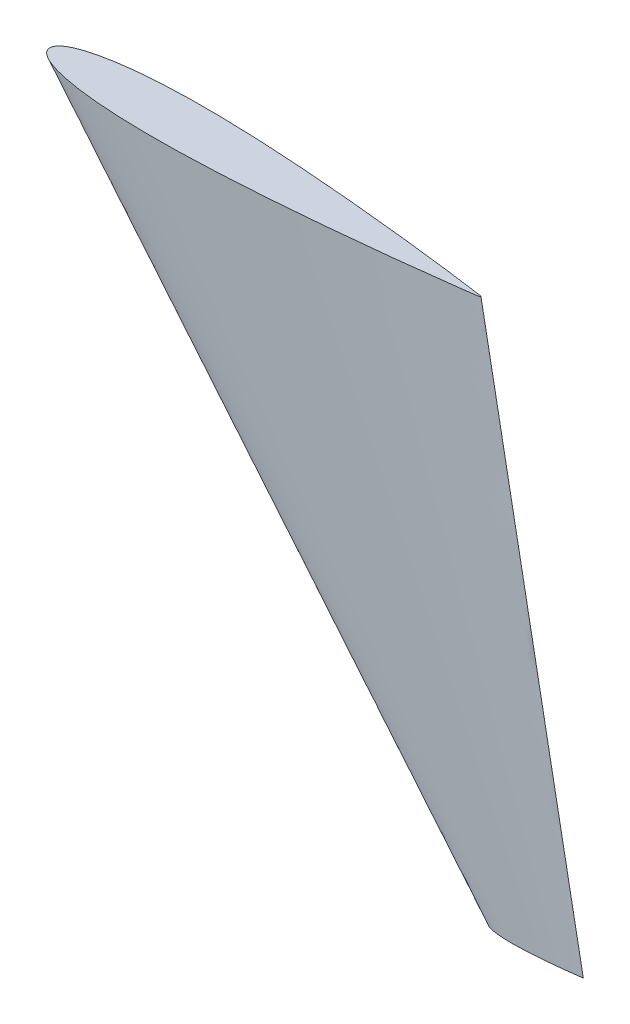
SolidWorks part; units mm, degrees
ref_plane "Front Plane" through (0, 0, 0) normal (0, 0, 1) x (1, 0, 0)
ref_plane "Top Plane" through (0, 0, 0) normal (0, 1, 0) x (1, 0, 0)
ref_plane "Right Plane" through (0, 0, 0) normal (1, 0, 0) x (0, 0, -1)
curve "Curve1"
  spline degree 3 poles (989.1889, 0, -3.124) (1003.9656, 0, 0) (989.1889, 0, 3.124) (979.4957, 0, 3.9602) (962.3964, 0, 6.4841) (943.9428, 0, 8.8491) (922.9132, 0, 11.6051) (900.2887, 0, 14.4478) (876.1894, 0, 17.4113) (850.9063, 0, 20.4351) (824.6249, 0, 23.4743) (797.5193, 0, 26.5234) (769.735, 0, 29.5334) (741.4059, 0, 32.5134) (712.6526, 0, 35.4198) (683.5857, 0, 38.2366) (654.3085, 0, 40.9505) (624.9168, 0, 43.5692) (595.4919, 0, 46.0176) (566.1196, 0, 48.3457) (536.8752, 0, 50.4873) (507.8364, 0, 52.4785) (479.0688, 0, 54.2437) (450.6418, 0, 55.8057) (422.6181, 0, 57.149) (395.0577, 0, 58.2561) (368.0197, 0, 59.0905) (341.5624, 0, 59.6944) (315.7376, 0, 59.999) (290.5993, 0, 60.0553) (266.1976, 0, 59.7899) (242.5818, 0, 59.2641) (219.7995, 0, 58.4267) (197.8965, 0, 57.3046) (176.9228, 0, 55.8955) (156.9193, 0, 54.1908) (137.9264, 0, 52.2182) (119.9888, 0, 49.9445) (103.1457, 0, 47.4173) (87.4377, 0, 44.6503) (72.9094, 0, 41.6113) (59.5881, 0, 38.3545) (47.5124, 0, 34.8789) (36.7185, 0, 31.1996) (27.2445, 0, 27.3184) (19.1092, 0, 23.264) (12.343, 0, 19.027) (6.9689, 0, 14.6049) (3.0199, 0, 9.972) (0.5665, 0, 5.0849) (-0.2745, 0, 0) (0.5665, 0, -5.0849) (3.0199, 0, -9.972) (6.9689, 0, -14.6049) (12.343, 0, -19.027) (19.1092, 0, -23.264) (27.2445, 0, -27.3184) (36.7185, 0, -31.1996) (47.5124, 0, -34.8789) (59.5881, 0, -38.3545) (72.9094, 0, -41.6113) (87.4377, 0, -44.6503) (103.1457, 0, -47.4173) (119.9888, 0, -49.9445) (137.9264, 0, -52.2182) (156.9193, 0, -54.1908) (176.9228, 0, -55.8955) (197.8965, 0, -57.3046) (219.7995, 0, -58.4267) (242.5818, 0, -59.2641) (266.1976, 0, -59.7899) (290.5993, 0, -60.0553) (315.7376, 0, -59.999) (341.5624, 0, -59.6944) (368.0197, 0, -59.0905) (395.0577, 0, -58.2561) (422.6181, 0, -57.149) (450.6418, 0, -55.8057) (479.0688, 0, -54.2437) (507.8364, 0, -52.4785) (536.8752, 0, -50.4873) (566.1196, 0, -48.3457) (595.4919, 0, -46.0176) (624.9168, 0, -43.5692) (654.3085, 0, -40.9505) (683.5857, 0, -38.2366) (712.6526, 0, -35.4198) (741.4059, 0, -32.5134) (769.735, 0, -29.5334) (797.5193, 0, -26.5234) (824.6249, 0, -23.4743) (850.9063, 0, -20.4351) (876.1894, 0, -17.4113) (900.2887, 0, -14.4478) (922.9132, 0, -11.6051) (943.9428, 0, -8.8491) (962.3964, 0, -6.4841) (979.4957, 0, -3.9602) (989.1889, 0, -3.124) (1003.9656, 0, 0) (989.1889, 0, 3.124) knots -0.01819 -0.010091 -0.003701 0 0.003701 0.010091 0.01819 0.027571 0.037978 0.04922 0.061159 0.073676 0.086676 0.10007 0.113795 0.12778 0.141967 0.156301 0.170733 0.185213 0.199702 0.214161 0.22855 0.24283 0.256971 0.270941 0.284704 0.298236 0.311509 0.32449 0.337159 0.349495 0.361463 0.373051 0.384237 0.394993 0.405307 0.415153 0.424519 0.43339 0.441745 0.449568 0.456846 0.463572 0.469733 0.475323 0.480337 0.484781 0.488676 0.492055 0.49498 0.497567 0.5 0.502433 0.50502 0.507945 0.511324 0.515219 0.519663 0.524677 0.530267 0.536428 0.543154 0.550432 0.558255 0.56661 0.575481 0.584847 0.594693 0.605007 0.615763 0.626949 0.638537 0.650505 0.662841 0.67551 0.688491 0.701764 0.715296 0.729059 0.743029 0.75717 0.77145 0.785839 0.800298 0.814787 0.829267 0.843699 0.858033 0.87222 0.886205 0.89993 0.913324 0.926324 0.938841 0.95078 0.962022 0.972429 0.98181 0.989909 0.996299 1 1.003701 1.010091 1.01819 periodic
sketch "Sketch2" plane through (0, 0, 0) normal (0, 1, 0) x (1, 0, 0)
  line L0 (8000, 0) -> (0, 0) construction
  line L1 (0, 0) -> (0, 395.0757) construction
  spline S1 degree 3 poles (7913.5111, -24.9917) (8031.7244, 0) (7913.5111, 24.9917) (7835.9656, 31.6818) (7699.1714, 51.8731) (7551.5421, 70.7926) (7383.3058, 92.8411) (7202.3097, 115.5825) (7009.5155, 139.2903) (6807.2507, 163.4811) (6596.999, 187.7941) (6380.1543, 212.1874) (6157.8798, 236.2671) (5931.2469, 260.1076) (5701.2206, 283.358) (5468.6854, 305.8929) (5234.4683, 327.6039) (4999.3345, 348.5532) (4763.9351, 368.1406) (4528.9569, 386.7656) (4295.002, 403.8987) (4062.6912, 419.8279) (3832.5502, 433.9494) (3605.1341, 446.4459) (3380.9452, 457.1923) (3160.4615, 466.0486) (2944.1578, 472.7239) (2732.499, 477.5553) (2525.9006, 479.9923) (2324.7946, 480.442) (2129.581, 478.3189) (1940.6547, 474.1131) (1758.3957, 467.4132) (1583.1723, 458.4372) (1415.3822, 447.1637) (1255.3541, 433.5267) (1103.4111, 417.7455) (959.9104, 399.5558) (825.1655, 379.3384) (699.5013, 357.2026) (583.2749, 332.8904) (476.7045, 306.8362) (380.0992, 279.0311) (293.7477, 249.5968) (217.9557, 218.5468) (152.8739, 186.1121) (98.7444, 152.2163) (55.7515, 116.8395) (24.1594, 79.7757) (4.532, 40.6789) (-2.1961, 0) (4.532, -40.6789) (24.1594, -79.7757) (55.7515, -116.8395) (98.7444, -152.2163) (152.8739, -186.1121) (217.9557, -218.5468) (293.7477, -249.5968) (380.0992, -279.0311) (476.7045, -306.8362) (583.2749, -332.8904) (699.5013, -357.2026) (825.1655, -379.3384) (959.9104, -399.5558) (1103.4111, -417.7455) (1255.3541, -433.5267) (1415.3822, -447.1637) (1583.1723, -458.4372) (1758.3957, -467.4132) (1940.6547, -474.1131) (2129.581, -478.3189) (2324.7946, -480.442) (2525.9006, -479.9923) (2732.499, -477.5553) (2944.1578, -472.7239) (3160.4615, -466.0486) (3380.9452, -457.1923) (3605.1341, -446.4459) (3832.5502, -433.9494) (4062.6912, -419.8279) (4295.002, -403.8987) (4528.9569, -386.7656) (4763.9351, -368.1406) (4999.3345, -348.5532) (5234.4683, -327.6039) (5468.6854, -305.8929) (5701.2206, -283.358) (5931.2469, -260.1076) (6157.8798, -236.2671) (6380.1543, -212.1874) (6596.999, -187.7941) (6807.2507, -163.4811) (7009.5155, -139.2903) (7202.3097, -115.5825) (7383.3058, -92.8411) (7551.5421, -70.7926) (7699.1714, -51.8731) (7835.9656, -31.6818) (7913.5111, -24.9917) (8031.7244, 0) (7913.5111, 24.9917) knots -0.01819 -0.010091 -0.003701 0 0.003701 0.010091 0.01819 0.027571 0.037978 0.04922 0.061159 0.073676 0.086676 0.10007 0.113795 0.12778 0.141967 0.156301 0.170733 0.185213 0.199702 0.214161 0.22855 0.24283 0.256971 0.270941 0.284704 0.298236 0.311509 0.32449 0.337159 0.349495 0.361463 0.373051 0.384237 0.394993 0.405307 0.415153 0.424519 0.43339 0.441745 0.449568 0.456846 0.463572 0.469733 0.475323 0.480337 0.484781 0.488676 0.492055 0.49498 0.497567 0.5 0.502433 0.50502 0.507945 0.511324 0.515219 0.519663 0.524677 0.530267 0.536428 0.543154 0.550432 0.558255 0.56661 0.575481 0.584847 0.594693 0.605007 0.615763 0.626949 0.638537 0.650505 0.662841 0.67551 0.688491 0.701764 0.715296 0.729059 0.743029 0.75717 0.77145 0.785839 0.800298 0.814787 0.829267 0.843699 0.858033 0.87222 0.886205 0.89993 0.913324 0.926324 0.938841 0.95078 0.962022 0.972429 0.98181 0.989909 0.996299 1 1.003701 1.010091 1.01819 only from (8000, 0) to (8000, 0)
  point P1 (0, 0)
  point P4 (0, 0)
  dimension "D1" = 8000
ref_plane "Plane1" through (0, -10000, 0) normal (0, 1, 0) x (1, 0, 0)
sketch "Sketch6" plane through (0, -10000, 0) normal (0, 1, 0) x (1, 0, 0)
  line L0 (9900, 0) -> (8150, 0) construction
  line L1 (8150, 0) -> (8150, 213.2137) construction
  line L2 (8000, 0) -> (0, 0) construction
  spline S1 degree 3 poles (9881.0805, -5.4669) (9906.9397, 0) (9881.0805, 5.4669) (9864.1175, 6.9304) (9834.1938, 11.3472) (9801.8998, 15.4859) (9765.0981, 20.309) (9725.5052, 25.2837) (9683.3315, 30.4697) (9639.0861, 35.7615) (9593.0935, 41.08) (9545.6587, 46.416) (9497.0362, 51.6834) (9447.4603, 56.8985) (9397.142, 61.9846) (9346.2749, 66.9141) (9295.0399, 71.6633) (9243.6044, 76.246) (9192.1108, 80.5308) (9140.7093, 84.605) (9089.5317, 88.3528) (9038.7137, 91.8374) (8988.3704, 94.9264) (8938.6231, 97.66) (8889.5818, 100.0108) (8841.3509, 101.9481) (8794.0345, 103.4083) (8747.7342, 104.4652) (8702.5408, 104.9983) (8658.5488, 105.0967) (8615.8458, 104.6323) (8574.5182, 103.7122) (8534.6491, 102.2466) (8496.3189, 100.2831) (8459.6149, 97.8171) (8424.6087, 94.834) (8391.3712, 91.3818) (8359.9804, 87.4028) (8330.505, 82.9803) (8303.0159, 78.1381) (8277.5914, 72.8198) (8254.2791, 67.1204) (8233.1467, 61.038) (8214.2573, 54.5993) (8197.6778, 47.8071) (8183.4412, 40.712) (8171.6003, 33.2973) (8162.1956, 25.5586) (8155.2849, 17.4509) (8150.9914, 8.8985) (8149.5196, 0) (8150.9914, -8.8985) (8155.2849, -17.4509) (8162.1956, -25.5586) (8171.6003, -33.2973) (8183.4412, -40.712) (8197.6778, -47.8071) (8214.2573, -54.5993) (8233.1467, -61.038) (8254.2791, -67.1204) (8277.5914, -72.8198) (8303.0159, -78.1381) (8330.505, -82.9803) (8359.9804, -87.4028) (8391.3712, -91.3818) (8424.6087, -94.834) (8459.6149, -97.8171) (8496.3189, -100.2831) (8534.6491, -102.2466) (8574.5182, -103.7122) (8615.8458, -104.6323) (8658.5488, -105.0967) (8702.5408, -104.9983) (8747.7342, -104.4652) (8794.0345, -103.4083) (8841.3509, -101.9481) (8889.5818, -100.0108) (8938.6231, -97.66) (8988.3704, -94.9264) (9038.7137, -91.8374) (9089.5317, -88.3528) (9140.7093, -84.605) (9192.1108, -80.5308) (9243.6044, -76.246) (9295.0399, -71.6633) (9346.2749, -66.9141) (9397.142, -61.9846) (9447.4603, -56.8985) (9497.0362, -51.6834) (9545.6587, -46.416) (9593.0935, -41.08) (9639.0861, -35.7615) (9683.3315, -30.4697) (9725.5052, -25.2837) (9765.0981, -20.309) (9801.8998, -15.4859) (9834.1938, -11.3472) (9864.1175, -6.9304) (9881.0805, -5.4669) (9906.9397, 0) (9881.0805, 5.4669) knots -0.01819 -0.010091 -0.003701 0 0.003701 0.010091 0.01819 0.027571 0.037978 0.04922 0.061159 0.073676 0.086676 0.10007 0.113795 0.12778 0.141967 0.156301 0.170733 0.185213 0.199702 0.214161 0.22855 0.24283 0.256971 0.270941 0.284704 0.298236 0.311509 0.32449 0.337159 0.349495 0.361463 0.373051 0.384237 0.394993 0.405307 0.415153 0.424519 0.43339 0.441745 0.449568 0.456846 0.463572 0.469733 0.475323 0.480337 0.484781 0.488676 0.492055 0.49498 0.497567 0.5 0.502433 0.50502 0.507945 0.511324 0.515219 0.519663 0.524677 0.530267 0.536428 0.543154 0.550432 0.558255 0.56661 0.575481 0.584847 0.594693 0.605007 0.615763 0.626949 0.638537 0.650505 0.662841 0.67551 0.688491 0.701764 0.715296 0.729059 0.743029 0.75717 0.77145 0.785839 0.800298 0.814787 0.829267 0.843699 0.858033 0.87222 0.886205 0.89993 0.913324 0.926324 0.938841 0.95078 0.962022 0.972429 0.98181 0.989909 0.996299 1 1.003701 1.010091 1.01819 only from (9900, 0) to (9900, 0)
  point P1 (8150, 0)
  dimension "D1" = 1750
  dimension "D2" = 8150
loft "Loft4" add profiles "Sketch6", "Sketch2" connector at (9898.3769, -10000, 1.2968) connector at (7999.9313, 0, 0.5436)
